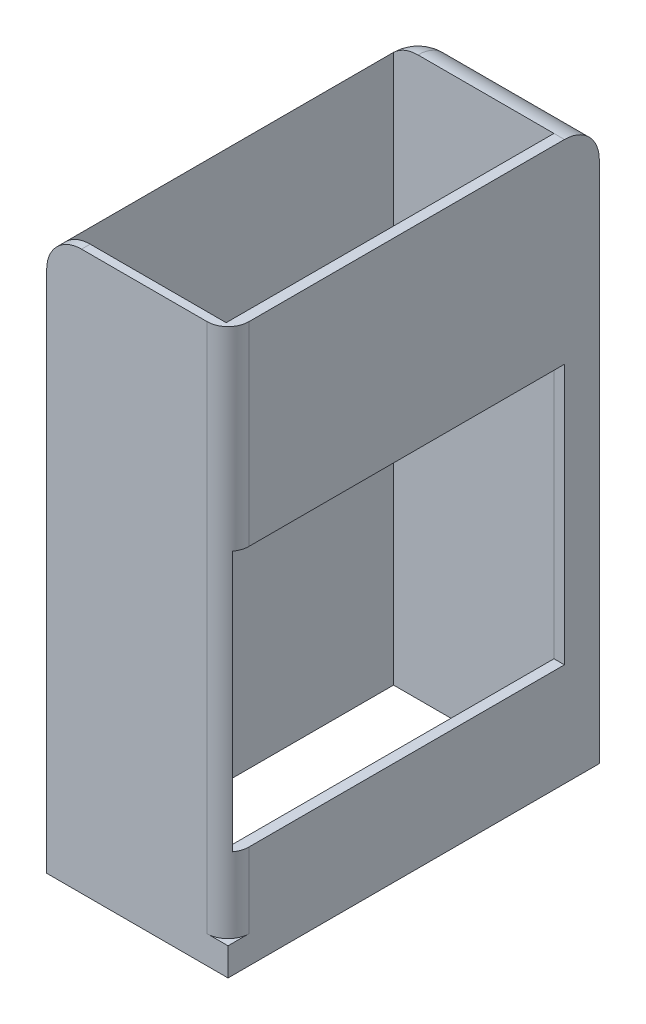
SolidWorks part; units mm, degrees
ref_plane "Front Plane" through (0, 0, 0) normal (0, 0, 1) x (1, 0, 0)
ref_plane "Top Plane" through (0, 0, 0) normal (0, 1, 0) x (1, 0, 0)
ref_plane "Right Plane" through (0, 0, 0) normal (1, 0, 0) x (0, 0, -1)
sketch "Sketch1" plane through (0, 0, 0) normal (0, 1, 0) x (1, 0, 0)
  line L10 (0, 152) -> (0, 101.37)
  line L11 (75, 101.37) -> (0, 101.37)
  line L12 (75, 101.37) -> (75, 191.352)
  line L13 (0, 152) -> (0, 192.37)
  line L14 (0, 192.37) -> (75, 192.37)
  line L15 (75, 192.37) -> (75, 191.352)
  dimension "D1" = 40.37
  dimension "D2" = 50.63
extrude "Boss-Extrude1" add sketch "Sketch1" along normal blind 4
sketch "Sketch2" plane through (0, 0, 0) normal (0, -1, 0) x (-1, 0, 0)
  line L13 (26, 91.37) -> (26, 176.9982)
  line L15 (-75, 192.37) -> (0, 192.37) construction
  line L17 (-80, 176.9982) -> (-80, 195.45)
  line L18 (-80, 195.45) -> (26, 195.45)
  line L19 (26, 195.45) -> (26, 176.9982)
  line L20 (-75, 192) -> (-75, 192.37)
  line L21 (-75, 192.37) -> (0, 192.37)
  line L23 (0, 192.37) -> (0, 101.37)
  line L24 (0, 101.37) -> (-75, 101.37)
  line L25 (-75, 101.37) -> (-75, 192)
  line L26 (-80, 91.37) -> (26, 91.37)
  line L27 (-80, 176.9982) -> (-80, 91.37)
  dimension "D2" = 10
  dimension "D3" = 3.08
  dimension "D4" = 3.08
extrude "Boss-Extrude2" add sketch "Sketch2" against normal blind 80
sketch "Sketch3" plane through (0, 0, 18) normal (0, 0, 1) x (1, 0, 0)
  line L0 (80, 0) -> (-26, 0) construction
  circle A0 centre (34.7654, 21.5) radius 8.5
  dimension "D1" = 17
  dimension "D2" = 21.5
extrude "Cut-Extrude1" cut sketch "Sketch3" against normal blind 171
sketch "Sketch4" plane through (0, 4, 0) normal (0, 1, 0) x (1, 0, 0)
  line L0 (69, 192.37) -> (75, 192.37) construction
  line L1 (0.5, 192.37) -> (68.5, 192.37)
  line L2 (0.5, 192.37) -> (0.5, 174.3675)
  line L3 (0.5, 174.3675) -> (68.5, 174.3675)
  line L4 (68.5, 192.37) -> (68.5, 174.3675)
  dimension "D1" = 0
  dimension "D2" = 68
extrude "Cut-Extrude2" cut sketch "Sketch4" against normal blind 116
sketch "Sketch5" plane through (0, 80, 0) normal (0, 1, 0) x (1, 0, 0)
  line L0 (0, -13.395) -> (0, 192.3675) construction
  line L1 (-24.5, 190.45) -> (-1.5, 190.45)
  line L2 (-24.5, 190.45) -> (-24.5, 143.45)
  line L3 (-24.5, 143.45) -> (-1.5, 143.45)
  line L4 (-1.5, 190.45) -> (-1.5, 143.45)
  line L5 (-26, 195.45) -> (80, 195.45) construction
  dimension "D1" = 23
  dimension "D2" = 1.5
  dimension "D3" = 47
  dimension "D4" = 5
extrude "Cut-Extrude3" cut sketch "Sketch5" against normal blind 110.2665
sketch "Sketch8" plane through (-1.5, 0, 0) normal (-1, 0, 0) x (0, 0, 1)
  line L0 (-190.4518, 14.7687) -> (-190.4518, 52.0904)
  line L1 (-190.4518, 52.0904) -> (-143.4518, 52.0904)
  line L2 (-143.4518, 52.0904) -> (-143.4518, 14.7687)
  line L3 (-143.4518, 14.7687) -> (-190.4518, 14.7687)
  line L5 (-195.4518, 120) -> (-195.4518, 0) construction
  dimension "D1" = 47
  dimension "D2" = 5
extrude "Cut-Extrude6" cut sketch "Sketch8" against normal blind 3.2665
fillet "Fillet2" radius 5 6 edges at (80, 40, -91.37) (27, 80, -91.37) (-26, 40, -195.45) (-26, 80, -143.41) (80, 40, -195.45) (27, 80, -195.45)
fillet "Fillet3" radius 5 2 edges at (-24.5355, 78.5355, -92.8345) (-26, 37.5, -91.37)
fillet "Fillet4" radius 5 3 edges at (80, 80, -143.41) (78.5355, 78.5355, -193.9855) (78.5355, 78.5355, -92.8345)
sketch "Sketch9" plane through (0, 80, 0) normal (0, 1, 0) x (1, 0, 0)
  line L3 (-26, 91.37) -> (80, 91.37)
  line L5 (-26, 91.37) -> (-26, 142.2154)
  line L6 (-26, 142.2154) -> (80, 142.2154)
  line L7 (80, 142.2154) -> (80, 91.37)
extrude "Cut-Extrude7" cut sketch "Sketch9" against normal blind 92
fillet "Fillet16" radius 10 1 edges at (75, 42, -142.2154)
fillet "Fillet18" radius 3 1 edges at (0, 42, -142.2154)
sketch "Sketch10" plane through (0, 0, 0) normal (0, -1, 0) x (1, 0, 0)
  line L0 (80, -190.45) -> (80, -142.2154) construction
  line L4 (80, -190.45) -> (80, -142.2154)
  line L5 (-26, -142.2154) -> (80, -142.2154) construction
  line L6 (0, -195.45) -> (0, -142.2154)
  line L10 (80, -190.45) -> (80, -195.45)
  line L11 (0, -195.45) -> (80, -195.45)
  line L12 (80, -142.2154) -> (0, -142.2154)
extrude "Cut-Extrude9" cut sketch "Sketch10" against normal blind 90
